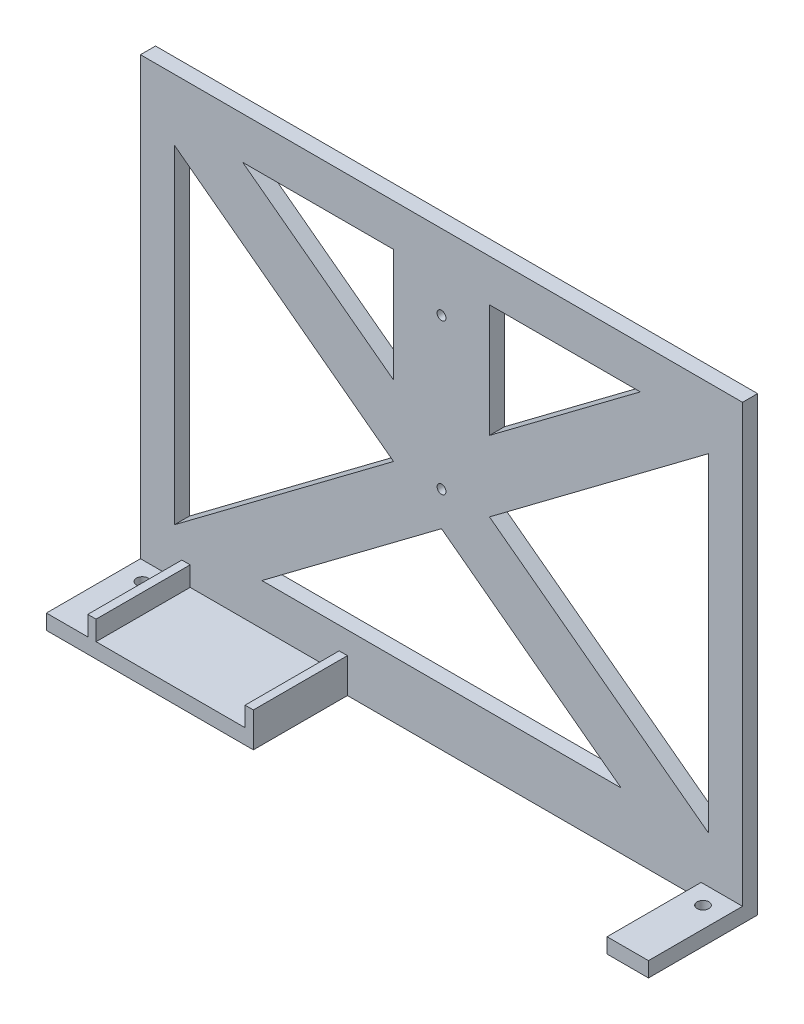
SolidWorks part; units mm, degrees
ref_plane "Front" through (0, 0, 0) normal (0, 0, 1) x (1, 0, 0)
ref_plane "Top" through (0, 0, 0) normal (0, 1, 0) x (1, 0, 0)
ref_plane "Right" through (0, 0, 0) normal (1, 0, 0) x (0, 0, -1)
sketch "Sketch1" plane through (0, 0, 0) normal (0, 0, 1) x (1, 0, 0)
  line L0 (-90.1289, 55.4552) -> (-90.1289, -55.4552)
  line L1 (-101.6, 76.2) -> (101.6, 76.2)
  line L2 (-101.6, 76.2) -> (-101.6, -76.2)
  line L3 (-101.6, -76.2) -> (101.6, -76.2)
  line L4 (101.6, 76.2) -> (101.6, -76.2)
  line L5 (-101.6, 76.2) -> (101.6, -76.2) construction
  line L6 (-101.6, -76.2) -> (101.6, 76.2) construction
  line L7 (0, -55) -> (0, 55) construction
  line L8 (-90.1289, -55.4552) -> (-16.1887, 0)
  line L9 (-16.1887, 0) -> (-90.1289, 55.4552)
  line L10 (55, 0) -> (-55, 0) construction
  line L11 (16.1887, 0) -> (90.1289, 55.4552)
  line L12 (90.1289, -55.4552) -> (16.1887, 0)
  line L13 (90.1289, 55.4552) -> (90.1289, -55.4552)
  line L14 (-16.1887, 61.9912) -> (-16.1887, 23.8125)
  line L15 (-16.1887, 23.8125) -> (-67.0937, 61.9912)
  line L16 (-67.0937, 61.9912) -> (-16.1887, 61.9912)
  line L17 (16.1887, 23.8125) -> (67.0937, 61.9912)
  line L18 (16.1887, 61.9912) -> (16.1887, 23.8125)
  line L19 (67.0937, 61.9912) -> (16.1887, 61.9912)
  line L20 (-60.6282, -57.0175) -> (0, -11.5463)
  line L21 (0, -11.5463) -> (60.6282, -57.0175)
  line L22 (60.6282, -57.0175) -> (-60.6282, -57.0175)
  circle A0 centre (0, 50.8) radius 1.5
  circle A2 centre (0, 0) radius 1.5
  point P0 (0, 0)
  point P23 (0, -11.5463)
  dimension "D3" = 3
  dimension "D4" = 50.8
  dimension "D6" = 19.05
  dimension "D1" = 203.2
  dimension "D2" = 152.4
  dimension "D5" = 25.4
extrude "Boss-Extrude1" add sketch "Sketch1" along normal blind 5.08 contours L4 L1 L2 L3 A2 A0 L19 L17 L18 L9 L8 L0 L11 L13 L12 L15 L16 L14 L21 L22 L20 region at (0, 73.66, 0)
sketch "Sketch2" plane through (0, 0, 5.08) normal (0, 0, 1) x (1, 0, 0)
  line L0 (-101.6, -76.2) -> (101.6, -76.2) construction
  line L1 (-101.6, -76.2) -> (-87.63, -76.2)
  line L2 (-101.6, -76.2) -> (-101.6, -71.12)
  line L3 (-101.6, -71.12) -> (-87.63, -71.12)
  line L4 (-87.63, -76.2) -> (-87.63, -71.12)
  line L5 (0, -55) -> (0, 55) construction
  line L6 (101.6, -71.12) -> (87.63, -71.12)
  line L7 (87.63, -76.2) -> (87.63, -71.12)
  line L8 (101.6, -76.2) -> (87.63, -76.2)
  line L9 (101.6, -76.2) -> (101.6, -71.12)
  line L11 (-87.63, -71.12) -> (-31.75, -71.12)
  line L12 (-87.63, -71.12) -> (-87.63, -76.2)
  line L13 (-87.63, -76.2) -> (-31.75, -76.2)
  line L14 (-31.75, -71.12) -> (-31.75, -76.2)
  line L15 (-87.63, -71.12) -> (-84.836, -71.12)
  line L16 (-87.63, -71.12) -> (-87.63, -64.5258)
  line L17 (-87.63, -64.5258) -> (-84.836, -64.5258)
  line L18 (-84.836, -71.12) -> (-84.836, -64.5258)
  line L19 (-31.75, -71.12) -> (-34.544, -71.12)
  line L20 (-31.75, -71.12) -> (-31.75, -64.5258)
  line L21 (-31.75, -64.5258) -> (-34.544, -64.5258)
  line L22 (-34.544, -71.12) -> (-34.544, -64.5258)
  line M10 (-101.6, -76.2) -> (101.6, -76.2)
  dimension "D1" = 5.08
  dimension "D2" = 55.88
  dimension "D3" = 50.292
  dimension "D4" = 13.97
  dimension "D5" = 31.75
extrude "Boss-Extrude2" add sketch "Sketch2" along normal blind 31.75 contours L4 L3 L2 M10 | L14 L11 L4 M10 | L9 L6 L7 M10 | L16 L15 L18 L17 | L20 L19 L22 L21 region at (-94.615, -73.66, 5.08) region at (94.615, -73.66, 5.08) region at (-59.69, -73.66, 5.08)
sketch "Sketch3" plane through (0, -71.12, 0) normal (0, 1, 0) x (1, 0, 0)
  line L4 (0, -55) -> (0, 55) construction
  line L10 (-101.6, -5.08) -> (-87.63, -5.08) construction
  line L11 (-101.6, -36.83) -> (-101.6, -5.08) construction
  circle A0 centre (-94.615, -11.43) radius 2
  circle A1 centre (94.615, -11.43) radius 2
  dimension "D1" = 4
  dimension "D2" = 6.35
  dimension "D3" = 6.985
extrude "Cut-Extrude1" cut sketch "Sketch3" against normal up to vertex (5.08 mm away) contours A0 | A1 region at (-94.615, -71.12, 11.43) region at (94.615, -71.12, 11.43) up to point (-101.6, -76.2, 36.83)
